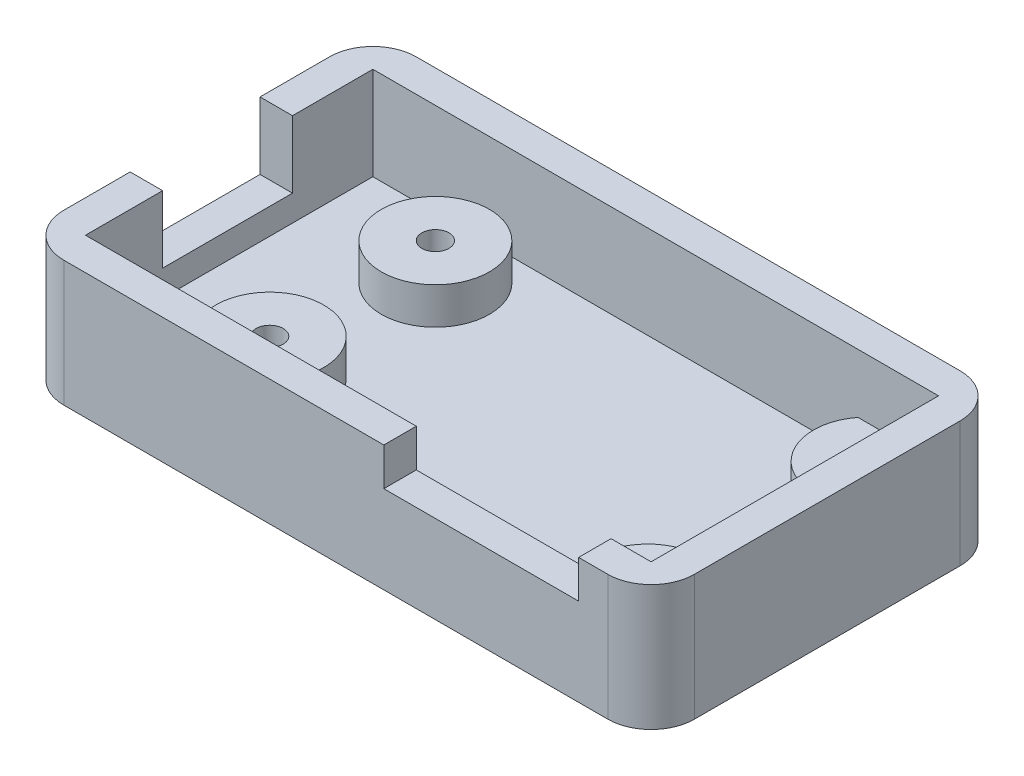
SolidWorks part; units mm, degrees
ref_plane "Front Plane" through (0, 0, 0) normal (0, 0, 1) x (1, 0, 0)
ref_plane "Top Plane" through (0, 0, 0) normal (0, 1, 0) x (1, 0, 0)
ref_plane "Right Plane" through (0, 0, 0) normal (1, 0, 0) x (0, 0, -1)
sketch "Sketch1" plane through (0, 0, 0) normal (0, 1, 0) x (1, 0, 0)
  line L0 (0.25, 0.25) -> (-52.02, 0.25)
  line L1 (0, 0) -> (-51.77, 0)
  line L2 (0, 0) -> (0, -26.06)
  line L3 (0, -26.06) -> (-51.77, -26.06)
  line L4 (-51.77, 0) -> (-51.77, -26.06)
  line L5 (-52.02, 0.25) -> (-52.02, -26.31)
  line L6 (0.25, -26.31) -> (-52.02, -26.31)
  line L7 (0.25, 0.25) -> (0.25, -26.31)
  line L8 (-0.75, 3.25) -> (-51.02, 3.25)
  line L9 (-55.02, -0.75) -> (-55.02, -25.31)
  line L10 (-0.75, -29.31) -> (-51.02, -29.31)
  line L11 (3.25, -0.75) -> (3.25, -25.31)
  line L12 (3.25, 3.25) -> (-55.02, 3.25) construction
  line L13 (-55.02, 3.25) -> (-55.02, -29.31) construction
  line L14 (3.25, 3.25) -> (3.25, -29.31) construction
  line L15 (3.25, -29.31) -> (-55.02, -29.31) construction
  circle A0 centre (-2.995, -3.06) radius 1.25
  circle A1 centre (-2.995, -23.38) radius 1.25
  circle A2 centre (-40.62, -5.375) radius 1.25
  circle A3 centre (-40.62, -20.685) radius 1.25
  circle A4 centre (-2.995, -3.06) radius 5
  circle A5 centre (-2.995, -23.38) radius 5
  circle A6 centre (-40.62, -20.685) radius 5
  circle A7 centre (-40.62, -5.375) radius 5
  arc A8 (-51.02, 3.25) -> (-55.02, -0.75) centre (-51.02, -0.75) ccw
  arc A9 (-0.75, 3.25) -> (3.25, -0.75) centre (-0.75, -0.75) cw
  arc A10 (-0.75, -29.31) -> (3.25, -25.31) centre (-0.75, -25.31) ccw
  arc A11 (-55.02, -25.31) -> (-51.02, -29.31) centre (-51.02, -25.31) ccw
  dimension "D6" = 2.5
  dimension "D7" = 15.31
  dimension "D12" = 10
  dimension "D13" = 4
  dimension "D1" = 26.06
  dimension "D2" = 51.77
  dimension "D3" = 20.32
  dimension "D4" = 3.06
  dimension "D5" = 2.995
  dimension "D8" = 5.375
  dimension "D9" = 11.15
  dimension "D10" = 0.25
  dimension "D11" = 3
extrude "Boss-Extrude1" add sketch "Sketch1" along normal blind 3 contours L9 A11 L10 A10 L11 A9 L8 A8
extrude "Boss-Extrude2" add sketch "Sketch1<3>" along normal blind 8.6 from surface contours L11 L8 L9 L10 L0 L7 L6 L5 | L7 A4 L0 | L6 A5 L7 region at (-3.2463, 0, -0.3741) region at (1.4304, 0, 21.3383) region at (1.6064, 0, -1.6064) starting at face at (-25.885, 3, 13.03)
sketch "Sketch1<3>" plane through (0, 0, 0) normal (0, 1, 0) x (1, 0, 0) same geometry as "Sketch1"
extrude "Boss-Extrude3" add sketch "Sketch1<4>" along normal blind 3.4 from surface contours L1 A4 L2 A0 | A7 A2 | A6 A3 | L2 A5 L3 A1 region at (-3.4746, 0, 0.1135) region at (-0.1109, 0, 22.7181) region at (-45.4786, 0, 20.685) region at (-45.4786, 0, 5.375) starting at face at (-25.885, 3, 13.03)
sketch "Sketch1<4>" plane through (0, 0, 0) normal (0, 1, 0) x (1, 0, 0) same geometry as "Sketch1"
sketch "Sketch2" plane through (0, 0, 26.31) normal (0, 0, -1) x (-1, 0, 0)
  line L0 (52.02, 11.6) -> (-0.25, 11.6) construction
  line L1 (3.45, 11.6) -> (21.45, 11.6)
  line L2 (3.45, 11.6) -> (3.45, 8.1)
  line L3 (3.45, 8.1) -> (21.45, 8.1)
  line L4 (21.45, 11.6) -> (21.45, 8.1)
  line L5 (7.2161, 6.4) -> (0, 6.4) construction
  line L6 (-0.25, 11.6) -> (-0.25, 3) construction
  dimension "D1" = 18
  dimension "D2" = 1.7
  dimension "D3" = 3.7
extrude "Cut-Extrude1" cut sketch "Sketch2" against normal up to next
sketch "Sketch4" plane through (-52.02, 0, 0) normal (1, 0, 0) x (0, 0, -1)
  line L0 (-26.31, 11.6) -> (0.25, 11.6) construction
  line L1 (-19.1793, 11.6) -> (-7.1793, 11.6)
  line L2 (-19.1793, 11.6) -> (-19.1793, 5.4)
  line L3 (-19.1793, 5.4) -> (-7.1793, 5.4)
  line L4 (-7.1793, 11.6) -> (-7.1793, 5.4)
  line L6 (0.25, 11.6) -> (0.25, 3) construction
  dimension "D1" = 12
  dimension "D2" = 7.4293
  dimension "D3" = 6.2
extrude "Cut-Extrude2" cut sketch "Sketch4" against normal up to next
extrude "Cut-Extrude3" cut sketch "Sketch1<5>" along normal through all contours A1 | A0 | A2 | A3 region at (-2.995, 0, 3.06) region at (-2.995, 0, 23.38) region at (-40.62, 0, 5.375) region at (-40.62, 0, 20.685)
sketch "Sketch1<5>" plane through (0, 0, 0) normal (0, 1, 0) x (1, 0, 0) same geometry as "Sketch1"
